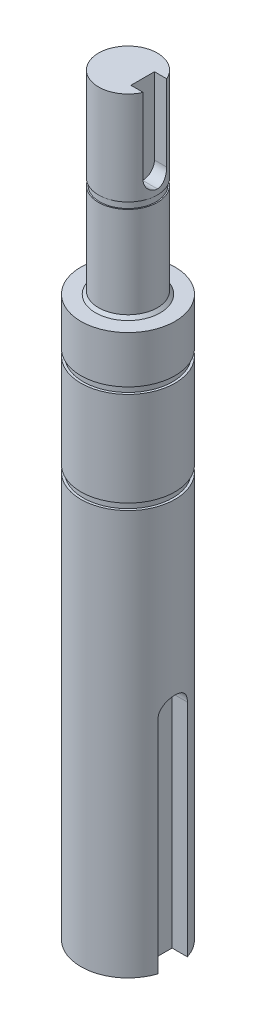
SolidWorks part; units mm, degrees
ref_plane "前视基准面" through (0, 0, 0) normal (0, 0, 1) x (1, 0, 0)
ref_plane "上视基准面" through (0, 0, 0) normal (0, 1, 0) x (1, 0, 0)
ref_plane "右视基准面" through (0, 0, 0) normal (1, 0, 0) x (0, 0, -1)
sketch "Sketch1" plane through (0, 0, 0) normal (0, 1, 0) x (1, 0, 0)
  circle A0 centre (0, 0) radius 5
  dimension "D1" = 10
extrude "Boss-Extrude1" add sketch "Sketch1" along normal blind 33
sketch "Sketch2" plane through (0, 0, 0) normal (0, -1, 0) x (1, 0, 0)
  circle A0 centre (0, 0) radius 8
  dimension "D1" = 16
extrude "Boss-Extrude2" add sketch "Sketch2" along normal blind 95
sketch "Sketch3" plane through (0, 0, 0) normal (0, 1, 0) x (1, 0, 0)
  circle A0 centre (0, 0) radius 7.6
  dimension "D1" = 15.2
extrude "Cut-Extrude1" cut sketch "Sketch3" against normal blind 1.1 from offset 8 flip side to cut offset against normal yes
extrude "Cut-Extrude2" cut sketch "Sketch3<2>" against normal blind 1.1 from offset 25.1 flip side to cut offset against normal yes
sketch "Sketch3<2>" plane through (0, 0, 0) normal (0, 1, 0) x (1, 0, 0) same geometry as "Sketch3"
sketch "Sketch4" plane through (0, 0, 0) normal (0, 1, 0) x (1, 0, 0)
  circle A0 centre (0, 0) radius 4.8
  dimension "D1" = 9.6
extrude "Cut-Extrude3" cut sketch "Sketch4" along normal blind 1.1 from offset 16 flip side to cut
sketch "Sketch5" plane through (0, -95, 0) normal (0, -1, 0) x (1, 0, 0)
  circle A0 centre (0, 0) radius 2.1
  dimension "D1" = 4.2
extrude "Cut-Extrude4" cut sketch "Sketch5" against normal blind 10
sketch "Sketch6" plane through (0, 33, 0) normal (0, 1, 0) x (1, 0, 0)
  line L0 (-9.8049, 0) -> (13.601, 0) construction
  line L1 (4.5826, 2) -> (2.5, 2)
  line L2 (2.5, 2) -> (2.5, -2)
  line L3 (2.5, -2) -> (4.5826, -2)
  circle A0 centre (0, 0) radius 5 construction
  arc A1 (4.5826, 2) -> (4.5826, -2) centre (0, 0) cw
  point P10 (5, 0)
  dimension "D1" = 4
  dimension "D2" = 2.5
extrude "Cut-Extrude5" cut sketch "Sketch6" against normal blind 15
fillet "Fillet1" radius 2 2 edges at (3.5413, 18, 2) (3.5413, 18, -2)
sketch "Sketch7" plane through (0, -95, 0) normal (0, -1, 0) x (1, 0, 0)
  line L0 (-12.8529, 0) -> (13.6572, 0) construction
  line L1 (7.5993, 2.5) -> (5, 2.5)
  line L2 (5, 2.5) -> (5, -2.5)
  line L3 (5, -2.5) -> (7.5993, -2.5)
  circle A0 centre (0, 0) radius 8 construction
  point P8 (8, 0)
  dimension "D1" = 5
  dimension "D2" = 3
extrude "Cut-Extrude6" cut sketch "Sketch7" against normal blind 40 and the other way through all
fillet "Fillet2" radius 2.5 2 edges at (6.2997, -55, 2.5) (6.2997, -55, -2.5)
chamfer "Chamfer1" distance 0.5 angle 45 1 edges at (0, 0, 5)
